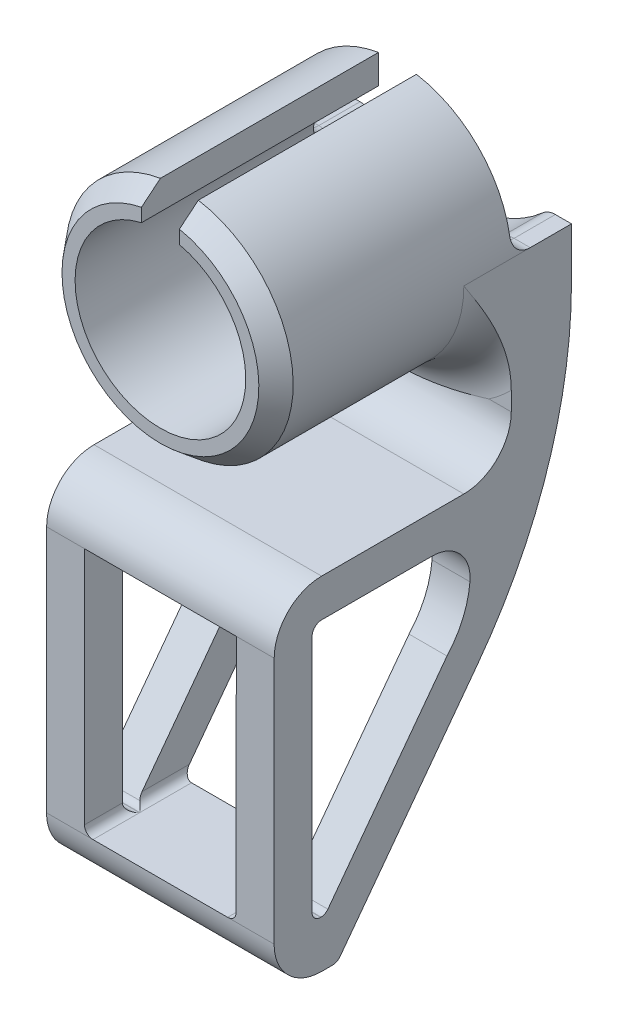
SolidWorks part; units mm, degrees
material "ABS"
ref_plane "Front Plane" through (0, 0, 0) normal (0, 0, 1) x (1, 0, 0)
ref_plane "Top Plane" through (0, 0, 0) normal (0, 1, 0) x (1, 0, 0)
ref_plane "Right Plane" through (0, 0, 0) normal (1, 0, 0) x (0, 0, -1)
sketch "Sketch1" plane through (0, 0, 0) normal (0, 0, 1) x (1, 0, 0)
  circle A0 centre (0, 0) radius 12
  dimension "D1" = 24
extrude "Boss-Extrude1" add sketch "Sketch1" along normal blind 25
sketch "Sketch2" plane through (0, 0, 25) normal (0, 0, 1) x (1, 0, 0)
  line L3 (-2, 12) -> (2, 12)
  line L7 (-2, 8.775) -> (-2, 12)
  line L10 (2, 8.775) -> (2, 12)
  arc A0 (-2, 8.775) -> (2, 8.775) centre (0, 0) ccw
  point P1 (0, 12)
  dimension "D1" = 18
  dimension "D4" = 4
  dimension "D6" = 12
extrude "Cut-Extrude1" cut sketch "Sketch2" against normal up to surface (25 mm away) up to face at (12, 0, 0)
sketch "Sketch3" plane through (0, 0, 0) normal (0, 0, -1) x (-1, 0, 0)
  line L0 (-9.5028, 0) -> (-12, 0)
  line L1 (9.5028, 0) -> (12, 0)
  line L2 (12, 0) -> (12, -19)
  line L3 (-12, 0) -> (-12, -19)
  line L4 (12, -19) -> (-12, -19)
  arc A0 (-9.5028, 0) -> (9.5028, 0) centre (0, 9.5) ccw
  circle A1 centre (0, 0) radius 12 construction
  point P11 (0, -3.937)
  dimension "D1" = 19
  dimension "D2" = 13.437
  dimension "D3" = 3.937
extrude "Boss-Extrude2" add sketch "Sketch3" along normal blind 6.35
fillet "Fillet1" radius 7.62 1 edges at (0, -9, 0)
fillet "Fillet2" [suppressed] radius 7.62
chamfer "Chamfer1" distance 2 angle 39 1 edges at (0, -12, 25) first distance on face at (0, 2.526, 8.3333)
sketch "Sketch6" plane through (0, -19, 0) normal (0, -1, 0) x (1, 0, 0)
  line L0 (-12, 25) -> (-12, -6.35)
  line L1 (-12, 25) -> (12, 25)
  line L2 (-12, -6.35) -> (12, -6.35)
  line L3 (12, 25) -> (12, -6.35)
  line L6 (10.3804, 25) -> (-10.3804, 25) construction
  point P1 (0, 0)
  point P9 (0, -6.35)
extrude "Boss-Extrude3" add sketch "Sketch6" along normal blind 3
sketch "Sketch7" plane through (12, 0, 0) normal (1, 0, 0) x (0, 0, -1)
  line L0 (-25, -22) -> (6.35, -22)
  line L2 (6.35, -22) -> (-18.3486, -55.1118)
  line L3 (-25.0132, -55.1118) -> (-18.3486, -55.1118)
  line L4 (-25, -22) -> (-25.0132, -55.1118)
extrude "Boss-Extrude4" add sketch "Sketch7" against normal up to surface (24 mm away) up to face at (-12, -13.6667, 6.2167)
fillet "Fillet3" radius 50 1 edges at (0, -22, -6.35)
fillet "Fillet7" radius 5 2 edges at (0, -19, 0) (0, -12, 0)
fillet "Fillet8" radius 5 1 edges at (0, -55.1118, 25.0132)
fillet "Fillet9" radius 5 1 edges at (0, -19, 25)
sketch "Sketch8" plane through (12, 0, 0) normal (1, 0, 0) x (0, 0, -1)
  line L29 (-5, -23) -> (-20.0008, -23)
  line L30 (-21.0008, -23.9996) -> (-21.0112, -50.1114)
  line L31 (-20.319, -51.0632) -> (-6.7779, -32.9096)
  line L32 (-5, -23) -> (-20.0008, -23)
  line L33 (-21.0008, -23.9996) -> (-21.0112, -50.1114)
  line L34 (-20.319, -51.0632) -> (-6.7779, -32.9096)
  arc A12 (-5, -23) -> (-6.7779, -32.9096) centre (-13.828, -26.5305) cw
  arc A16 (-20.0008, -23) -> (-21.0008, -23.9996) centre (-20.0008, -24) ccw
  arc A17 (-21.0112, -50.1114) -> (-20.319, -51.0632) centre (-20.0112, -50.1118) ccw
  arc A18 (-6.7779, -32.9096) -> (-0.7142, -21.914) centre (-43.65, -5.406) ccw
  arc A19 (-5, -23) -> (-0.7142, -21.914) centre (-5, -14) ccw
  arc A20 (-20.0008, -23) -> (-21.0008, -23.9996) centre (-20.0008, -24) ccw
  arc A21 (-21.0112, -50.1114) -> (-20.319, -51.0632) centre (-20.0112, -50.1118) ccw
  dimension "D1" = 4
extrude "Cut-Extrude2" cut sketch "Sketch8" against normal up to surface (24 mm away) up to face at (-12, -22.5457, 8.155)
fillet "Fillet10" radius 1 1 edges at (0, -55.1118, 18.3486)
fillet "Fillet12" radius 2 2 edges at (-9.5028, 0, -3.175) (9.5028, 0, -3.175)
fillet "Fillet13" radius 2 4 edges at (-9.5981, -0.1265, 0) (-11.1491, 0, 0) (9.5981, -0.1265, 0) (11.1491, 0, 0)
sketch "Sketch9" plane through (0, 0.0099, 24.9913) normal (0, 0.0004, 1) x (1, 0, 0)
  line L0 (12, -24.0079) -> (-12, -24.0079) construction
  line L1 (-8, -50.1197) -> (8, -50.1197)
  line L2 (-8, -50.1197) -> (-8, -24.0079)
  line L3 (-8, -24.0079) -> (8, -24.0079)
  line L4 (8, -50.1197) -> (8, -24.0079)
  line L5 (-12, -50.1197) -> (12, -50.1197) construction
  line L6 (12, -55.1197) -> (-12, -55.1197) construction
  line L7 (-12, -50.1197) -> (-12, -24.0079) construction
  point P9 (0, -55.1197)
  point P12 (0, -24.0079)
  dimension "D1" = 4
extrude "Cut-Extrude3" cut sketch "Sketch9" against normal up to surface (10.3905 mm away) up to face at (0, -45.0054, 10.8102)
fillet "Fillet14" [suppressed] radius 0.5
fillet "Fillet15" radius 4 1 edges at (0, -23, 5)
sketch "Sketch10" plane through (0, -50.1197, 0.0199) normal (0, 1, -0.0004) x (1, 0, 0)
  line L1 (-12, -19.5895) -> (12, -19.5895)
  line L2 (-12, -19.5895) -> (-12, -20.9913)
  line L3 (-12, -20.9913) -> (12, -20.9913)
  line L4 (12, -19.5895) -> (12, -20.9913)
extrude "Boss-Extrude5" add sketch "Sketch10" against normal up to next
fillet "Fillet16" radius 0.9 8 edges at (10, -50.1114, 21.0112) (10, -50.1119, 19.6094) (8, -50.1106, 23.0112) (8, -50.1129, 17.115) (-8, -50.1129, 17.115) (-8, -50.1106, 23.0112) (-10, -50.1114, 21.0112) (-10, -50.1119, 19.6094)
